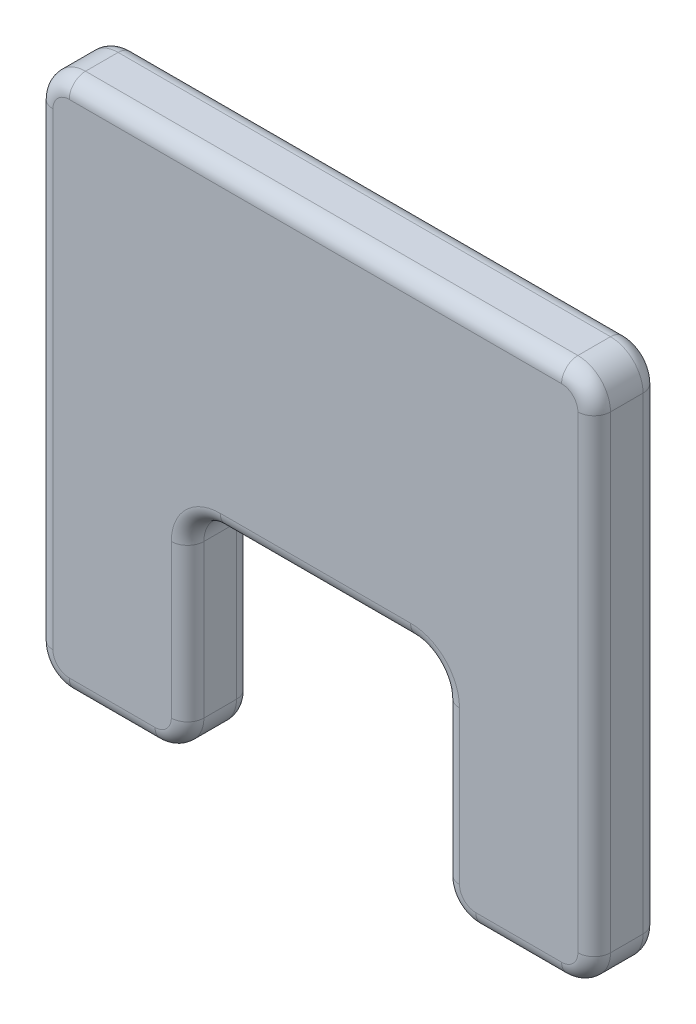
SolidWorks part; units mm, degrees
material "Polyurethane Foam Flexible"
ref_plane "Front Plane" through (0, 0, 0) normal (0, 0, 1) x (1, 0, 0)
ref_plane "Top Plane" through (0, 0, 0) normal (0, 1, 0) x (1, 0, 0)
ref_plane "Right Plane" through (0, 0, 0) normal (1, 0, 0) x (0, 0, -1)
sketch "Sketch1" plane through (0, 0, 0) normal (0, 0, 1) x (1, 0, 0)
  line L0 (-93.2955, 250.6666) -> (-93.2955, -223.9129) construction
  line L1 (-93.2955, 185.6621) -> (341.3045, 185.6621)
  line L2 (-93.2955, 185.6621) -> (-93.2955, -230.2629)
  line L3 (-93.2955, -230.2629) -> (24.3822, -230.2629)
  line L4 (341.3045, 185.6621) -> (341.3045, -230.2629)
  line L5 (223.6267, -230.2629) -> (341.3045, -230.2629)
  line L7 (24.3822, -230.2629) -> (24.3822, -60.2629)
  line L8 (24.3822, -60.2629) -> (223.6267, -60.2629)
  line L9 (223.6267, -230.2629) -> (223.6267, -60.2629)
  line L10 (24.3822, -223.9129) -> (24.3822, -60.2629) construction
  line L11 (16.7045, -230.2629) -> (-93.2955, -230.2629) construction
  line L12 (341.3045, -223.9129) -> (341.3045, 250.6666) construction
  dimension "D1" = 415.925
extrude "Boss-Extrude1" add sketch "Sketch1" along normal blind 50.8
fillet "Fillet1" radius 25.4 8 edges at (24.3822, -230.2629, 25.4) (-93.2955, -230.2629, 25.4) (-93.2955, 185.6621, 25.4) (341.3045, 185.6621, 25.4) (341.3045, -230.2629, 25.4) (223.6267, -230.2629, 25.4) (223.6267, -60.2629, 25.4) (24.3822, -60.2629, 25.4)
fillet "Fillet2" radius 12.7 32 edges at (31.8217, -67.7023, 0) (124.0045, -60.2629, 0) (216.1872, -67.7023, 0) (223.6267, -145.2629, 0) (231.0662, -222.8234, 0) (282.4656, -230.2629, 0) (333.865, -222.8234, 0) (341.3045, -22.3004, 0) (333.865, 178.2227, 0) (124.0045, 185.6621, 0) (-85.856, 178.2227, 0) (-93.2955, -22.3004, 0) (-85.856, -222.8234, 0) (-34.4566, -230.2629, 0) (16.9428, -222.8234, 0) (24.3822, -145.2629, 0) (-85.856, -222.8234, 50.8) (-93.2955, -22.3004, 50.8) (-85.856, 178.2227, 50.8) (124.0045, 185.6621, 50.8) (333.865, 178.2227, 50.8) (341.3045, -22.3004, 50.8) (333.865, -222.8234, 50.8) (282.4656, -230.2629, 50.8) (231.0662, -222.8234, 50.8) (223.6267, -145.2629, 50.8) (216.1872, -67.7023, 50.8) (124.0045, -60.2629, 50.8) (31.8217, -67.7023, 50.8) (24.3822, -145.2629, 50.8) (16.9428, -222.8234, 50.8) (-34.4566, -230.2629, 50.8)
